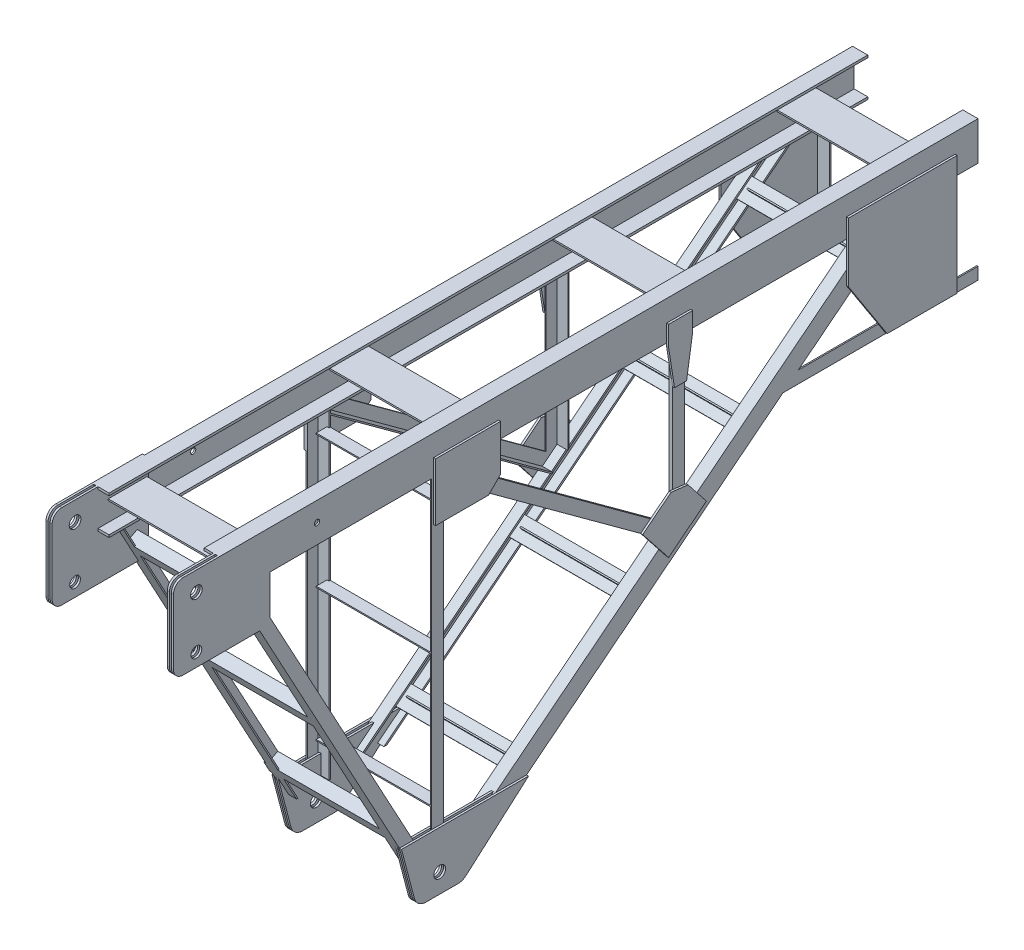
SolidWorks part; units mm, degrees
ref_plane "前视基准面" through (0, 0, 0) normal (0, 0, 1) x (1, 0, 0)
ref_plane "上视基准面" through (0, 0, 0) normal (0, 1, 0) x (1, 0, 0)
ref_plane "右视基准面" through (0, 0, 0) normal (1, 0, 0) x (0, 0, -1)
sketch "草图2" plane through (0, 0, 0) normal (0, 0, 1) x (1, 0, 0)
  line L0 (0, 0) -> (0, 160)
  line L1 (0, 160) -> (63, 160)
  line L2 (63, 160) -> (63, 150)
  line L3 (63, 150) -> (6.5, 150)
  line L4 (6.5, 150) -> (6.5, 10)
  line L5 (6.5, 10) -> (63, 10)
  line L6 (63, 10) -> (63, 0)
  line L7 (63, 0) -> (0, 0)
  line L8 (457, 160) -> (520, 160)
  line L9 (520, 160) -> (520, 0)
  line L10 (520, 0) -> (457, 0)
  line L11 (457, 0) -> (457, 10)
  line L12 (457, 10) -> (513.5, 10)
  line L13 (513.5, 10) -> (513.5, 150)
  line L14 (513.5, 150) -> (457, 150)
  line L15 (457, 150) -> (457, 160)
  dimension "D1" = 160
  dimension "D2" = 10
  dimension "D3" = 6.5
  dimension "D4" = 63
  dimension "D5" = 520
extrude "拉伸1" add sketch "草图2" along normal blind 3335
sketch "草图5" plane through (0, 0, 0) normal (-1, 0, 0) x (0, 0, 1)
  line L0 (160, 95) -> (320, 95)
  line L1 (320, 95) -> (320, 88.5)
  line L2 (243.25, 88.5) -> (320, 88.5)
  line L3 (243.25, 88.5) -> (243.25, 48.5)
  line L4 (243.25, 48.5) -> (236.75, 48.5)
  line L5 (236.75, 48.5) -> (236.75, 88.5)
  line L6 (236.75, 88.5) -> (160, 88.5)
  line L7 (160, 88.5) -> (160, 95)
  line L8 (0, 160) -> (0, 0) construction
  point P10 (0, 80)
  dimension "D1" = 160
  dimension "D2" = 6.5
  dimension "D3" = 6.5
  dimension "D4" = 40
  dimension "D5" = 160
  dimension "D6" = 15
extrude "拉伸3" add sketch "草图5" against normal blind 511.5
sketch "草图11" plane through (0, 0, 0) normal (-1, 0, 0) x (0, 0, 1)
  line L0 (3335, 160) -> (3335, 0) construction
  line L1 (3335, 80) -> (0, 80) construction
  line L2 (0, 160) -> (0, 0) construction
  circle A0 centre (3240, 80) radius 24.25
  dimension "D1" = 48.5
  dimension "D2" = 95
extrude "拉伸10" cut sketch "草图11" against normal through all
pattern_linear "阵列(线性)1" count 4 spacing 927.5 along (0, 0, 1) of "拉伸3"
sketch "草图12" plane through (0, 0, 0) normal (-1, 0, 0) x (0, 0, 1)
  line L0 (3240, 80) -> (0, 80) construction
  line L1 (0, 160) -> (0, 0) construction
  line L2 (2240, 80) -> (2240, -1500) construction
  line L3 (3095, 80) -> (2240, -1500) construction
  line L4 (2240, -1500) -> (240, 80) construction
  line L5 (3335, 10) -> (3335, 150) construction
  line L6 (276.7391, 0) -> (2175.4733, -1500)
  line L7 (3335, 0) -> (0, 0) construction
  line L8 (2175.4733, -1500) -> (2268.4257, -1500)
  line L9 (2268.4257, -1500) -> (3080.1345, 0)
  line L10 (3080.1345, 0) -> (3023.2832, 0)
  line L11 (3023.2832, 0) -> (2265, -1401.2718)
  line L12 (2265, -1401.2718) -> (2265, 0)
  line L13 (2265, 0) -> (2215, 0)
  line L14 (2215, 0) -> (2215, -1429.2739)
  line L15 (2215, -1429.2739) -> (405.7925, 0)
  line L16 (405.7925, 0) -> (276.7391, 0)
  point P9 (3335, 80)
  dimension "D2" = 240
  dimension "D3" = 240
  dimension "D4" = 1000
  dimension "D5" = 40
  dimension "D6" = 80
  dimension "D7" = 50
  dimension "D8" = 25
  dimension "D9" = 25
  dimension "D10" = 50
  dimension "D11" = 1580
extrude "拉伸11" add sketch "草图12" against normal blind 50
pattern_linear "阵列(线性)2" count 2 spacing 470 along (1, 0, 0) of "拉伸11"
sketch "草图15" plane through (50, 0, 0) normal (1, 0, 0) x (0, 0, -1)
  line L0 (-2265, 0) -> (-2220, 0)
  line L1 (-2265, 0) -> (-2215, 0) construction
  line L2 (-2220, 0) -> (-2220, -1500)
  line L3 (-2175.4733, -1500) -> (-2268.4257, -1500) construction
  line L4 (-2220, -1500) -> (-2262.7406, -1500)
  line L5 (-2262.7406, -1500) -> (-3074.4494, 0)
  line L6 (-3080.1345, 0) -> (-3023.2832, 0) construction
  line L7 (-3074.4494, 0) -> (-3023.2832, 0)
  line L8 (-3023.2832, 0) -> (-2265, -1401.2718)
  line L9 (-2265, -1401.2718) -> (-2265, 0)
  line L10 (-2215, 0) -> (-2215, -1429.2739) construction
  line L11 (-2268.4257, -1500) -> (-3080.1345, 0) construction
  dimension "D1" = 5
  dimension "D2" = 5
extrude "拉伸12" cut sketch "草图15" against normal blind 45
sketch "草图16" plane through (50, 0, 0) normal (1, 0, 0) x (0, 0, -1)
  line L0 (-405.7925, 0) -> (-276.7391, 0)
  line L1 (-276.7391, 0) -> (-2175.4733, -1500)
  line L2 (-2175.4733, -1500) -> (-2215, -1500)
  line L3 (-2175.4733, -1500) -> (-2220, -1500) construction
  line L4 (-2215, -1500) -> (-2215, -1429.2739)
  line L5 (-2215, -1429.2739) -> (-405.7925, 0)
  line L6 (-2220, -1500) -> (-2220, 0) construction
extrude "拉伸13" cut sketch "草图16" against normal blind 7
sketch "草图17" plane through (43, 0, 0) normal (1, 0, 0) x (0, 0, -1)
  line L0 (-2188.3787, -1500) -> (-2215, -1500)
  line L1 (-2215, -1500) -> (-2175.4733, -1500) construction
  line L2 (-2215, -1500) -> (-2215, -1439.4691)
  line L3 (-2215, -1439.4691) -> (-392.8872, 0)
  line L4 (-392.8872, 0) -> (-289.6445, 0)
  line L5 (-276.7391, 0) -> (-405.7925, 0) construction
  line L6 (-289.6445, 0) -> (-2188.3787, -1500)
  line L7 (-2175.4733, -1500) -> (-276.7391, 0) construction
  line L8 (-405.7925, 0) -> (-2215, -1429.2739) construction
  dimension "D1" = 8
  dimension "D2" = 8
extrude "拉伸14" cut sketch "草图17" against normal blind 38
sketch "草图18" plane through (470, 0, 0) normal (-1, 0, 0) x (0, 0, 1)
  line L0 (3074.4494, 0) -> (3023.2832, 0)
  line L2 (3023.2832, 0) -> (2265, -1401.2718)
  line L3 (2265, -1401.2718) -> (2265, 0)
  line L4 (2265, 0) -> (2220, 0)
  line L6 (2220, 0) -> (2220, -1500)
  line L7 (2175.4733, -1500) -> (2268.4257, -1500) construction
  line L8 (2220, -1500) -> (2262.7406, -1500)
  line L9 (2262.7406, -1500) -> (3074.4494, 0)
  line L10 (2268.4257, -1500) -> (3080.1345, 0) construction
  line L11 (2215, 0) -> (2215, -1429.2739) construction
  line L12 (3023.2832, 0) -> (2265, 0) construction
  line L13 (3335, 0) -> (3080.1345, 0) construction
  dimension "D1" = 5
  dimension "D2" = 5
extrude "拉伸15" cut sketch "草图18" against normal blind 45
sketch "草图19" plane through (470, 0, 0) normal (-1, 0, 0) x (0, 0, 1)
  line L0 (289.6445, 0) -> (392.8872, 0)
  line L1 (392.8872, 0) -> (2215, -1439.4691)
  line L2 (2215, -1439.4691) -> (2215, -1500)
  line L3 (2175.4733, -1500) -> (2220, -1500) construction
  line L4 (2215, -1500) -> (2188.3787, -1500)
  line L5 (2188.3787, -1500) -> (289.6445, 0)
  line L6 (2220, 0) -> (2220, -1500) construction
  line L7 (2215, 0) -> (405.7925, 0) construction
  line L8 (2215, -1429.2739) -> (405.7925, 0) construction
  line L9 (276.7391, 0) -> (2175.4733, -1500) construction
  line L12 (2215, 0) -> (2215, -1429.2739) construction
  dimension "D1" = 8
  dimension "D2" = 8
extrude "拉伸16" cut sketch "草图19" against normal blind 2
sketch "草图20" plane through (472, 0, 0) normal (-1, 0, 0) x (0, 0, 1)
  line L0 (290.4511, 0) -> (392.0806, 0)
  line L1 (2175.4733, -1500) -> (2268.4257, -1500) construction
  line L2 (392.0806, 0) -> (2215, -1440.1063)
  line L3 (2215, -1440.1063) -> (2215, -1500)
  line L4 (2215, -1500) -> (2189.1852, -1500)
  line L6 (2189.1852, -1500) -> (290.4511, 0)
  line L7 (2215, -1429.2739) -> (405.7925, 0) construction
  line L9 (2215, 0) -> (405.7925, 0) construction
  line L10 (276.7391, 0) -> (2175.4733, -1500) construction
  line L11 (2215, 0) -> (2215, -1429.2739) construction
  dimension "D1" = 8.5
  dimension "D2" = 8.5
extrude "拉伸17" cut sketch "草图20" against normal blind 42.7
sketch "草图21" plane through (520, 0, 0) normal (1, 0, 0) x (0, 0, -1)
  line L0 (-2265, -1401.2718) -> (-2265, 0) construction
  line L1 (-2265, -75) -> (-2215, -75)
  line L2 (-2265, -75) -> (-2265, -125)
  line L3 (-2265, -125) -> (-2215, -125)
  line L4 (-2215, -75) -> (-2215, -125)
  line L5 (-2215, 0) -> (-2215, -1429.2739) construction
  line L6 (-3335, 0) -> (-3080.1345, 0) construction
  dimension "D1" = 50
  dimension "D2" = 75
extrude "拉伸18" add sketch "草图21" against normal blind 478.5
pattern_linear "阵列(线性)3" count 3 spacing 550 along (0, -1, 0) of "拉伸18"
sketch "草图25" plane through (0, 0, 2265) normal (0, 0, 1) x (1, 0, 0)
  line L0 (41.5, -125) -> (515, -125) construction
  line L1 (5, -80) -> (515, -80)
  line L2 (5, -80) -> (5, -125)
  line L3 (5, -125) -> (515, -125)
  line L4 (515, -80) -> (515, -125)
  line L5 (41.5, -75) -> (515, -75) construction
  line L6 (5, 0) -> (5, -1401.2718) construction
  line L7 (515, -625) -> (515, -125) construction
  line L8 (41.5, -675) -> (515, -675) construction
  line L9 (515, -1175) -> (515, -675) construction
  line L10 (5, -675) -> (515, -675)
  line L11 (5, -675) -> (5, -630)
  line L12 (5, -630) -> (515, -630)
  line L13 (515, -675) -> (515, -630)
  line L14 (41.5, -625) -> (515, -625) construction
  line L15 (515, -1401.2718) -> (515, -1225) construction
  line L16 (5, -1225) -> (515, -1225)
  line L17 (5, -1225) -> (5, -1180)
  line L18 (5, -1180) -> (515, -1180)
  line L19 (515, -1225) -> (515, -1180)
  line L20 (41.5, -1175) -> (515, -1175) construction
  line L21 (5, 0) -> (5, -1401.2718) construction
  line L22 (41.5, -675) -> (515, -675) construction
  line L23 (41.5, -1225) -> (515, -1225) construction
  dimension "D1" = 5
  dimension "D2" = 5
  dimension "D3" = 5
extrude "拉伸19" cut sketch "草图25" against normal blind 45
sketch "草图26" plane through (520, 0, 0) normal (1, 0, 0) x (0, 0, -1)
  line L0 (-2982.6977, -75) -> (-3026.672, -98.7962)
  line L1 (-2982.6977, -75) -> (-2958.9015, -118.9743)
  line L2 (-3026.672, -98.7962) -> (-3002.8758, -142.7705)
  line L3 (-2958.9015, -118.9743) -> (-3002.8758, -142.7705)
  line L4 (-3023.2832, 0) -> (-2265, -1401.2718) construction
  line L5 (-2268.4257, -1500) -> (-3080.1345, 0) construction
  line L6 (-3335, 0) -> (-3080.1345, 0) construction
  dimension "D1" = 50
  dimension "D2" = 75
extrude "拉伸20" add sketch "草图26" against normal blind 528.5
pattern_linear "阵列(线性)4" count 3 spacing 625 along (0, -0.8795, -0.4759) of "拉伸20"
sketch "草图27" plane through (0, -1265.4526, 2338.4971) normal (0, 0.4759, -0.8795) x (-1, 0, 0)
  line L0 (-5, -154.4302) -> (-5, 53.5774) construction
  line L1 (-515, 1303.5774) -> (-5, 1303.5774)
  line L2 (-515, 1303.5774) -> (-515, 1348.5774)
  line L3 (-515, 1348.5774) -> (-5, 1348.5774)
  line L4 (-5, 1303.5774) -> (-5, 1348.5774)
  line L5 (-5, 678.5774) -> (-515, 678.5774)
  line L6 (-5, 678.5774) -> (-5, 723.5774)
  line L7 (-5, 723.5774) -> (-515, 723.5774)
  line L8 (-515, 678.5774) -> (-515, 723.5774)
  line L9 (-515, 53.5774) -> (-5, 53.5774)
  line L10 (-515, 53.5774) -> (-515, 98.5774)
  line L11 (-515, 98.5774) -> (-5, 98.5774)
  line L12 (-5, 53.5774) -> (-5, 98.5774)
  line L13 (-5, 103.5774) -> (-515, 103.5774) construction
  line L14 (-5, 728.5774) -> (-515, 728.5774) construction
  line L15 (-515, 678.5774) -> (-515, 103.5774) construction
  line L16 (-5, 728.5774) -> (-5, 1303.5774) construction
  line L17 (-5, 1353.5774) -> (-515, 1353.5774) construction
  line L18 (-5, 1303.5774) -> (-515, 1303.5774) construction
  dimension "D1" = 5
  dimension "D2" = 5
  dimension "D3" = 5
extrude "拉伸21" cut sketch "草图27" against normal blind 45
sketch "草图29" plane through (0, 0, 0) normal (-1, 0, 0) x (0, 0, 1)
  line L0 (440.2354, -75) -> (503.01, -124.5919)
  line L1 (440.2354, -75) -> (437.136, -78.9234)
  line L2 (503.01, -124.5919) -> (499.9105, -128.5153)
  line L3 (437.136, -78.9234) -> (499.9105, -128.5153)
  line L4 (2215, -1429.2739) -> (405.7925, 0) construction
  line L5 (2215, 0) -> (405.7925, 0) construction
  line L6 (2215, -1429.2739) -> (2165.4081, -1492.0485) construction
  line L7 (276.7391, 0) -> (2175.4733, -1500) construction
  line L8 (405.7925, 0) -> (356.2006, -62.7745) construction
  line L9 (380.9966, -31.3873) -> (2190.2041, -1460.6612) construction
  dimension "D1" = 75
  dimension "D2" = 2.5
  dimension "D3" = 80
  dimension "D4" = 2.5
extrude "拉伸22" add sketch "草图29" against normal blind 520
sketch "草图30" plane through (0, 167.9613, 132.6895) normal (0, 0.7847, 0.6199) x (1, 0, 0)
  line L1 (44.85, -429.4372) -> (474.85, -429.4372)
  line L2 (44.85, -429.4372) -> (44.85, -434.4372)
  line L3 (44.85, -434.4372) -> (474.85, -434.4372)
  line L4 (474.85, -429.4372) -> (474.85, -434.4372)
  line L9 (259.85, -429.4372) -> (259.85, -391.9372) construction
  line L10 (514.7, -391.9372) -> (5, -391.9372) construction
  line L11 (259.85, -471.9372) -> (259.85, -434.4372) construction
  line L12 (514.7, -471.9372) -> (5, -471.9372) construction
  dimension "D1" = 430
  dimension "D2" = 5
extrude "拉伸23" add sketch "草图30" along normal blind 15
pattern_linear "阵列(线性)5" count 4 spacing 600 along (0, -0.6199, 0.7847) of "拉伸22", "拉伸23"
sketch "草图31" plane through (520, 0, 0) normal (1, 0, 0) x (0, 0, -1)
  line L1 (-2398.2991, -1260) -> (-1871.6759, -1260)
  line L2 (-2398.2991, -1260) -> (-2335, -1500)
  line L3 (-2335, -1500) -> (-2145, -1500)
  line L4 (-1871.6759, -1260) -> (-2145, -1500)
  line L5 (-2268.4257, -1500) -> (-3080.1345, 0) construction
  line L6 (-276.7391, 0) -> (-2175.4733, -1500) construction
  line L9 (-2265, 0) -> (-2335, -1500) construction
  line L10 (-2145, -1500) -> (-2215, 0) construction
  line L11 (-2175.4733, -1500) -> (-2268.4257, -1500) construction
  dimension "D1" = 190
  dimension "D3" = 240
extrude "拉伸24" add sketch "草图31" along normal blind 8.5
pattern_linear "阵列(线性)6" count 2 spacing 17 along (-1, 0, 0) of "拉伸24"
pattern_linear "阵列(线性)7" count 2 spacing 511.5 along (-1, 0, 0) of "拉伸24", "阵列(线性)6"
sketch "草图33" plane through (0, -1500, 0) normal (0, -1, 0) x (1, 0, 0)
  line L0 (503, 2241.3703) -> (17, 2241.3703) construction
  line L1 (503, 2262.7406) -> (503, 2220) construction
  line L2 (17, 2262.7406) -> (17, 2220) construction
  line L3 (520, 1871.6759) -> (520, 2175.4733) construction
  line L4 (520, 2041.3703) -> (511.5, 2041.3703)
  line L5 (520, 2041.3703) -> (520, 2441.3703)
  line L6 (520, 2441.3703) -> (511.5, 2441.3703)
  line L7 (511.5, 2041.3703) -> (511.5, 2441.3703)
  line L8 (511.5, 2175.4733) -> (511.5, 2145) construction
  line L10 (8.5, 2041.3703) -> (0, 2041.3703)
  line L11 (8.5, 2041.3703) -> (8.5, 2441.3703)
  line L12 (8.5, 2441.3703) -> (0, 2441.3703)
  line L13 (0, 2041.3703) -> (0, 2441.3703)
  line L15 (8.5, 2262.7406) -> (8.5, 2220) construction
  line L16 (0, 2335) -> (0, 2268.4257) construction
  dimension "D1" = 200
  dimension "D2" = 200
  dimension "D3" = 200
  dimension "D4" = 200
extrude "拉伸26" cut sketch "草图33" against normal blind 160
fillet "圆角1" radius 50 9 edges at (524.25, -1500, 2335) (524.25, -1500, 2145) (507.25, -1500, 2335) (507.25, -1500, 2145) (12.75, -1500, 2335) (12.75, -1500, 2145) (-4.25, -1500, 2335) (-4.25, -1500, 2145)
sketch "草图35" plane through (-8.5, 0, 0) normal (-1, 0, 0) x (0, 0, 1)
  circle A0 centre (2240, -1420) radius 24.25
  circle A1 centre (3240, 80) radius 24.25 construction
  dimension "D3" = 48.5
  dimension "D1" = 1500
  dimension "D2" = 1000
extrude "拉伸27" cut sketch "草图35" against normal through all
sketch "草图36" plane through (0, -1500, 0) normal (0, -1, 0) x (1, 0, 0)
  line L0 (503, 2262.7406) -> (503, 2220) construction
  line L1 (503, 2472.7406) -> (17, 2472.7406)
  line L2 (503, 2472.7406) -> (503, 1972.7406)
  line L3 (503, 1972.7406) -> (17, 1972.7406)
  line L4 (17, 2472.7406) -> (17, 1972.7406)
  line L5 (17, 2262.7406) -> (17, 2220) construction
  line L6 (503, 2262.7406) -> (470, 2262.7406) construction
  dimension "D1" = 500
  dimension "D2" = 210
extrude "拉伸28" cut sketch "草图36" against normal blind 160
sketch "草图37" plane through (0, 0, 3335) normal (0, 0, 1) x (1, 0, 0)
  line L0 (0, 160) -> (0, 0) construction
  line L1 (8.5, 160) -> (511.5, 160)
  line L2 (8.5, 160) -> (8.5, 0)
  line L3 (8.5, 0) -> (511.5, 0)
  line L4 (511.5, 160) -> (511.5, 0)
  line L5 (520, 0) -> (520, 160) construction
  line L6 (520, 160) -> (457, 160) construction
  line L7 (457, 0) -> (520, 0) construction
  dimension "D1" = 8.5
  dimension "D2" = 8.5
extrude "拉伸29" cut sketch "草图37" against normal blind 190
sketch "草图38" plane through (6.5, 0, 0) normal (1, 0, 0) x (0, 0, -1)
  line L0 (-3335, 150) -> (-2862.5, 150)
  line L1 (-3335, 150) -> (0, 150) construction
  line L2 (-2862.5, 150) -> (-2792.5, 80)
  line L3 (-2792.5, 80) -> (-2862.5, 10)
  line L4 (-2862.5, 10) -> (-3335, 10)
  line L5 (-3335, 10) -> (-3335, 150) construction
  line L6 (-3335, 10) -> (-3335, 150)
  line L7 (-3335, 10) -> (0, 10) construction
  line L8 (-2792.5, 80) -> (-3240, 80) construction
  line L9 (-2862.5, 150) -> (-2862.5, 10) construction
  line L10 (-2942.5, 95) -> (-2942.5, 88.5) construction
  dimension "D1" = 80
extrude "拉伸30" add sketch "草图38" along normal blind 2
pattern_linear "阵列(线性)8" count 2 spacing 505 along (1, 0, 0) of "拉伸30"
sketch "草图39" plane through (0, 0, 0) normal (-1, 0, 0) x (0, 0, 1)
  line L1 (3335, 160) -> (2935, 160)
  line L2 (3335, 160) -> (3335, -190)
  line L3 (3335, -190) -> (2977.3181, -190)
  line L4 (2398.2991, -1260) -> (2407.9702, -1242.1282) construction
  line L6 (3335, 160) -> (0, 160) construction
  line L7 (2977.3181, -190) -> (2935, -163.1432)
  line L8 (3023.2832, 0) -> (2982.6977, -75) construction
  line L9 (2935, 160) -> (2935, -163.1432)
  dimension "D1" = 350
  dimension "D2" = 400
extrude "拉伸31" add sketch "草图39" along normal blind 8.5
pattern_linear "阵列(线性)9" count 2 spacing 17 along (1, 0, 0) of "拉伸31"
sketch "草图40" plane through (-8.5, 0, 0) normal (-1, 0, 0) x (0, 0, 1)
  line L0 (3240, 160) -> (3240, -190) construction
  line L1 (3335, 160) -> (2935, 160) construction
  line L3 (3335, -190) -> (3335, 160) construction
  line L4 (2977.3181, -190) -> (3335, -190) construction
  circle A0 centre (3240, 80) radius 24.25
  dimension "D2" = 48.5
  dimension "D1" = 95
  dimension "D3" = 80
extrude "拉伸32" cut sketch "草图40" against normal through all
sketch "草图41" plane through (0, 0, 3335) normal (0, 0, 1) x (1, 0, 0)
  line L0 (17, 160) -> (-8.5, 160) construction
  line L1 (8.5, 0) -> (0, 0)
  line L2 (8.5, 0) -> (8.5, 160)
  line L3 (8.5, 160) -> (0, 160)
  line L4 (0, 0) -> (0, 160)
  line L5 (0, -190) -> (0, 0) construction
extrude "拉伸33" cut sketch "草图41" against normal blind 190
sketch "草图42" plane through (6.5, 0, 0) normal (1, 0, 0) x (0, 0, -1)
  line L0 (-2862.5, 150) -> (0, 150) construction
  line L1 (-3035, 150) -> (-2935, 150)
  line L2 (-3035, 150) -> (-3035, 10)
  line L3 (-3035, 10) -> (-2935, 10)
  line L4 (-2935, 150) -> (-2935, 10)
  line L5 (-2862.5, 10) -> (0, 10) construction
  line L6 (-2935, 0) -> (-2935, -163.1432) construction
  dimension "D1" = 100
extrude "拉伸34" add sketch "草图42" along normal blind 2
sketch "草图43" plane through (6.5, 0, 0) normal (1, 0, 0) x (0, 0, -1)
  line L1 (-2792.5, 10) -> (-2935, 10)
  line L2 (-2792.5, 10) -> (-2792.5, 150)
  line L3 (-2792.5, 150) -> (-2935, 150)
  line L4 (-2935, 10) -> (-2935, 150)
  line L5 (-2862.5, 150) -> (0, 150) construction
extrude "拉伸36" cut sketch "草图43" along normal blind 2
sketch "草图48" plane through (0, 0, 0) normal (-1, 0, 0) x (0, 0, 1)
  line L0 (276.7391, 0) -> (0, 0) construction
  line L1 (95, 0) -> (145, 0)
  line L2 (95, 0) -> (95, -370)
  line L3 (95, -370) -> (145, -370)
  line L4 (145, 0) -> (145, -370)
  line L5 (0, 160) -> (0, 0) construction
  dimension "D1" = 50
  dimension "D2" = 370
  dimension "D3" = 95
extrude "拉伸40" add sketch "草图48" against normal blind 520 separate body
sketch "草图49" plane through (0, -370, 0) normal (0, -1, 0) x (1, 0, 0)
  line L0 (5, 95) -> (5, 140)
  line L1 (520, 95) -> (0, 95) construction
  line L2 (5, 140) -> (50, 140)
  line L3 (50, 140) -> (50, 145)
  line L4 (520, 145) -> (0, 145) construction
  line L5 (50, 145) -> (470, 145)
  line L6 (470, 145) -> (470, 140)
  line L7 (470, 140) -> (515, 140)
  line L8 (515, 140) -> (515, 95)
  line L9 (515, 95) -> (5, 95)
  line L10 (0, 95) -> (0, 145) construction
  line L11 (520, 95) -> (520, 145) construction
  dimension "D1" = 5
  dimension "D2" = 5
  dimension "D3" = 50
  dimension "D4" = 5
extrude "拉伸41" cut sketch "草图49" against normal blind 370
sketch "草图50" plane through (0, 0, 0) normal (-1, 0, 0) x (0, 0, 1)
  line L0 (95, -370) -> (145, -370) construction
  line L1 (0, -370) -> (745.0936, -370)
  line L2 (0, -370) -> (0, -420)
  line L3 (0, -420) -> (808.3847, -420)
  line L4 (745.0936, -370) -> (808.3847, -420)
  line L5 (276.7391, 0) -> (1871.6759, -1260) construction
  line L7 (0, 160) -> (0, 0) construction
  dimension "D1" = 50
extrude "拉伸42" add sketch "草图50" against normal blind 50
pattern_linear "阵列(线性)10" count 2 spacing 470 along (1, 0, 0) of "拉伸42"
sketch "草图51" plane through (50, 0, 0) normal (1, 0, 0) x (0, 0, -1)
  line L0 (0, -370) -> (0, -420) construction
  line L1 (-140, -370) -> (0, -370)
  line L2 (-140, -370) -> (-140, -415)
  line L3 (-140, -415) -> (0, -415)
  line L4 (0, -370) -> (0, -415)
  line L5 (0, -420) -> (-808.3847, -420) construction
  line L6 (-802.0556, -415) -> (-745.0936, -370)
  line L7 (-808.3847, -420) -> (-745.0936, -370) construction
  line L8 (-745.0936, -370) -> (-145, -370)
  line L9 (-745.0936, -370) -> (-145, -370) construction
  line L10 (-145, -370) -> (-145, -415)
  line L11 (-145, -415) -> (-802.0556, -415)
  line L12 (-145, 0) -> (-145, -370) construction
  dimension "D1" = 5
extrude "拉伸43" cut sketch "草图51" against normal blind 45
sketch "草图52" plane through (470, 0, 0) normal (-1, 0, 0) x (0, 0, 1)
  line L0 (0, -370) -> (0, -420) construction
  line L1 (140, -370) -> (0, -370)
  line L2 (140, -370) -> (140, -415)
  line L3 (140, -415) -> (0, -415)
  line L4 (0, -370) -> (0, -415)
  line L5 (0, -420) -> (808.3847, -420) construction
  line L6 (145, -370) -> (145, -415)
  line L7 (145, -415) -> (802.0556, -415)
  line L9 (802.0556, -415) -> (745.0936, -370)
  line L10 (745.0936, -370) -> (145, -370)
  line L11 (276.7391, 0) -> (745.0936, -370) construction
  dimension "D1" = 5
extrude "拉伸44" cut sketch "草图52" against normal blind 45
sketch "草图53" plane through (50, 0, 0) normal (1, 0, 0) x (0, 0, -1)
  line L0 (-145, -370) -> (-145, -420)
  line L1 (-145, 0) -> (-145, -415) construction
  line L2 (0, -420) -> (-808.3847, -420) construction
  line L3 (-145, -420) -> (-95, -420)
  line L4 (-95, -420) -> (-95, -415)
  line L5 (-140, -415) -> (0, -415) construction
  line L6 (-95, -415) -> (-140, -415)
  line L7 (-140, -415) -> (-140, -370)
  line L8 (-140, 0) -> (-140, -415) construction
  line L9 (-140, -370) -> (-145, -370)
  dimension "D1" = 50
  dimension "D2" = 50
extrude "拉伸45" add sketch "草图53" along normal blind 420
sketch "草图55" plane through (0, 0, 0) normal (-1, 0, 0) x (0, 0, 1)
  line L0 (0, 80) -> (2935, 80) construction
  line L1 (0, 160) -> (0, 0) construction
  line L2 (2935, 160) -> (2935, 0) construction
  line L3 (0, -420) -> (808.3847, -420) construction
  line L6 (95, 80) -> (95, -415)
  line L7 (95, -415) -> (385, -415)
  line L8 (385, -415) -> (545, -167.5)
  line L9 (545, -167.5) -> (545, 80)
  line L10 (545, 80) -> (95, 80)
  line L12 (95, -167.5) -> (545, -167.5) construction
  dimension "D1" = 95
  dimension "D2" = 290
  dimension "D3" = 450
  dimension "D4" = 5
extrude "拉伸46" add sketch "草图55" along normal blind 8.5
pattern_linear "阵列(线性)11" count 2 spacing 528.5 along (1, 0, 0) of "拉伸46"
sketch "草图59" plane through (0, 0, 0) normal (-1, 0, 0) x (0, 0, 1)
  line L0 (1250, 0) -> (1250, -666.9239) construction
  line L1 (2215, 0) -> (545, 0) construction
  line L2 (2000.7292, -1260) -> (545, -109.9739) construction
  line L3 (0, 160) -> (0, 0) construction
  line L4 (1225, 0) -> (1275, 0)
  line L5 (1275, 0) -> (1275, -686.6739)
  line L6 (1275, -686.6739) -> (1225, -647.1739)
  line L7 (1225, -647.1739) -> (1225, 0)
  dimension "D1" = 1250
  dimension "D2" = 25
  dimension "D3" = 25
extrude "拉伸49" add sketch "草图59" against normal blind 50
sketch "草图60" plane through (0, 0, 0) normal (-1, 0, 0) x (0, 0, 1)
  line L0 (1275, -686.6739) -> (2215, 0) construction
  line L1 (1275, -655.7139) -> (2172.6183, 0)
  line L2 (1275, -686.6739) -> (1275, 0) construction
  line L3 (2172.6183, 0) -> (2215, 0)
  line L4 (2215, 0) -> (2215, -30.96)
  line L5 (2215, -30.96) -> (1295.3617, -702.7597)
  line L6 (2000.7292, -1260) -> (1275, -686.6739) construction
  line L7 (1295.3617, -702.7597) -> (1275, -686.6739)
  line L8 (1275, -686.6739) -> (1275, -655.7139)
  line L9 (2215, 0) -> (1275, 0) construction
  dimension "D1" = 50
  dimension "D2" = 25
extrude "拉伸50" add sketch "草图60" against normal blind 50
pattern_linear "阵列(线性)15" count 2 spacing 478.5 along (1, 0, 0) of "拉伸49", "拉伸50"
sketch "草图61" plane through (50, 0, 0) normal (1, 0, 0) x (0, 0, -1)
  line L0 (-2172.6183, 0) -> (-2215, 0)
  line L1 (-2215, 0) -> (-2215, -24.768)
  line L3 (-2215, -24.768) -> (-1291.2893, -699.5425)
  line L4 (-1225, -647.1739) -> (-1295.3617, -702.7597) construction
  line L5 (-1291.2893, -699.5425) -> (-1230, -651.1239)
  line L6 (-1230, -651.1239) -> (-1230, 0)
  line L7 (-1275, 0) -> (-1225, 0) construction
  line L8 (-1230, 0) -> (-1275, 0)
  line L9 (-1275, 0) -> (-1275, -655.7139)
  line L10 (-1275, -655.7139) -> (-2172.6183, 0)
  line L11 (-1295.3617, -702.7597) -> (-2215, -30.96) construction
  line L12 (-1225, 0) -> (-1225, -647.1739) construction
  line L13 (-2215, -30.96) -> (-2215, -75) construction
  dimension "D1" = 5
  dimension "D2" = 5
extrude "拉伸51" cut sketch "草图61" against normal blind 45
sketch "草图63" plane through (470, 0, 0) normal (-1, 0, 0) x (0, 0, 1)
  line L0 (2172.6183, 0) -> (2215, 0)
  line L1 (2172.6183, 0) -> (1275, -655.7139)
  line L2 (1275, -655.7139) -> (1275, 0)
  line L3 (1275, 0) -> (1230, 0)
  line L4 (1275, 0) -> (1225, 0) construction
  line L5 (1230, 0) -> (1230, -651.1239)
  line L6 (1230, -651.1239) -> (1291.2893, -699.5425)
  line L7 (1291.2893, -699.5425) -> (2215, -24.768)
  line L8 (2101.995, -1340) -> (405.7925, 0) construction
  line L9 (1225, 0) -> (1225, -647.1739) construction
  line L10 (1295.3617, -702.7597) -> (2215, -30.96) construction
  line L11 (1275, -655.7139) -> (1275, 0) construction
  line L13 (2220, 0) -> (2215, 0) construction
  line L14 (2215, 0) -> (2215, -24.768)
  line L15 (2220, 0) -> (2220, -75) construction
  dimension "D1" = 5
  dimension "D2" = 5
  dimension "D3" = 5
extrude "拉伸53" cut sketch "草图63" against normal blind 45
sketch "草图64" plane through (0, 0, 0) normal (-1, 0, 0) x (0, 0, 1)
  line L0 (2935, 160) -> (0, 160) construction
  line L3 (1200, 80) -> (1225, 0) construction
  line L4 (1200, 80) -> (1300, 80)
  line L5 (1200, 80) -> (1200, 0)
  line L6 (2265, -1260) -> (2265, 0) construction
  line L7 (1300, 80) -> (1300, 0)
  line L8 (1275, 0) -> (1300, 80) construction
  line L9 (1995.9732, 80) -> (2265, 80)
  line L10 (2172.6183, 0) -> (1275, 0) construction
  line L11 (1225, 0) -> (545, 0) construction
  line L12 (1200, 0) -> (1225, -160)
  line L13 (1225, 0) -> (1225, -647.1739) construction
  line L14 (1225, -160) -> (1275, -160)
  line L15 (1275, -655.7139) -> (1275, 0) construction
  line L16 (1275, -160) -> (1300, 0)
  line L17 (808.3847, -420) -> (1871.6759, -1260) construction
  line L18 (1995.9732, 80) -> (1995.9732, -160)
  line L19 (1995.9732, -160) -> (2265, -160)
  line L20 (1142.6825, -633.1191) -> (1299.6188, -757.0989)
  line L21 (1142.6825, -633.1191) -> (1250, -497.2741)
  line L22 (1299.6188, -757.0989) -> (1406.9364, -621.2539)
  line L23 (1250, -497.2741) -> (1406.9364, -621.2539)
  line L24 (1295.3617, -702.7597) -> (2215, -30.96) construction
  line L25 (1250, 80) -> (1250, -497.2741) construction
  line L27 (2265, 80) -> (2265, -160)
  line L28 (2172.6183, 0) -> (1275, -655.7139) construction
  dimension "D1" = 100
  dimension "D2" = 240
  dimension "D3" = 40
  dimension "D4" = 200
  dimension "D5" = 80
  dimension "D6" = 25
  dimension "D7" = 240
extrude "拉伸54" add sketch "草图64" along normal blind 8.5
pattern_linear "阵列(线性)16" count 2 spacing 537 along (1, 0, 0) of "拉伸54"
chamfer "倒角1" distance 50 angle 45 4 edges at (532.75, -497.2741, 1250) (-4.25, -497.2741, 1250) (-4.25, -160, 1995.9732) (532.75, -160, 1995.9732)
pattern_linear "阵列(线性)17" count 2 spacing 520 along (1, 0, 0) of "拉伸31"
pattern_linear "阵列(线性)18" count 2 spacing 503 along (1, 0, 0) of "拉伸31"
sketch "草图65" plane through (520, 0, 0) normal (1, 0, 0) x (0, 0, -1)
  line L0 (-3335, -190) -> (-3335, 160) construction
  line L1 (-3335, 160) -> (0, 160) construction
  circle A0 centre (-3240, 80) radius 24.25
  circle A1 centre (-3240, -135) radius 22.25
  dimension "D2" = 48.5
  dimension "D3" = 44.5
  dimension "D1" = 95
  dimension "D4" = 80
  dimension "D5" = 215
  dimension "D6" = 95
extrude "拉伸55" cut sketch "草图65" against normal through all
fillet "圆角3" radius 40 8 edges at (12.75, -190, 3335) (-4.25, -190, 3335) (515.75, -190, 3335) (498.75, -190, 3335) (515.75, 160, 3335) (498.75, 160, 3335) (12.75, 160, 3335) (-4.25, 160, 3335)
sketch "草图66" plane through (520, 0, 0) normal (1, 0, 0) x (0, 0, -1)
  line L0 (-3240, 80) -> (0, 80) construction
  line L1 (0, 0) -> (0, 160) construction
  circle A0 centre (-2740, 80) radius 11
  dimension "D1" = 22
  dimension "D2" = 500
extrude "拉伸56" cut sketch "草图66" against normal through all
